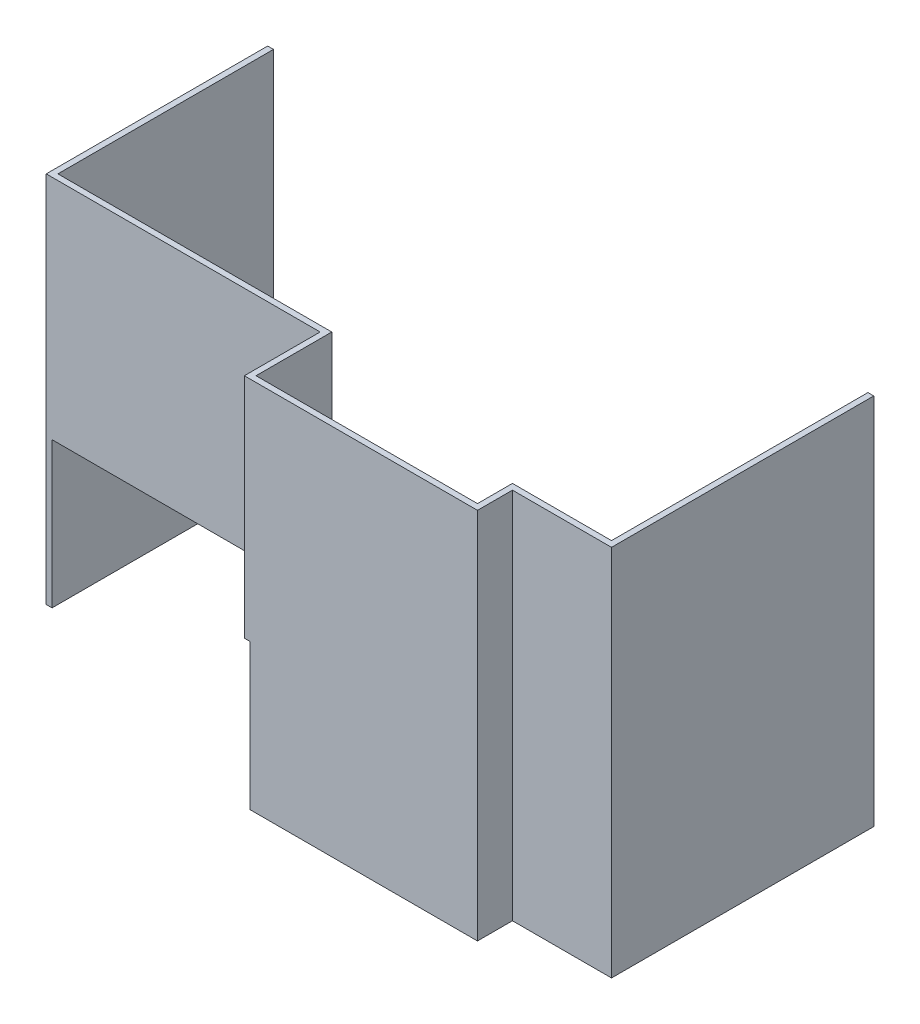
SolidWorks part; units mm, degrees
ref_plane "Front Plane" through (0, 0, 0) normal (0, 0, 1) x (1, 0, 0)
ref_plane "Top Plane" through (0, 0, 0) normal (0, 1, 0) x (1, 0, 0)
ref_plane "Right Plane" through (0, 0, 0) normal (1, 0, 0) x (0, 0, -1)
sketch "Sketch1" plane through (0, 0, 0) normal (0, 1, 0) x (1, 0, 0)
  line L0 (0, 0) -> (0, 241.3)
  line L1 (0, 241.3) -> (6.35, 241.3)
  line L2 (6.35, 241.3) -> (6.35, 6.35)
  line L3 (6.35, 6.35) -> (304.8, 6.35)
  line L4 (0, 0) -> (298.45, 0)
  line L5 (298.45, 0) -> (298.45, -82.55)
  line L6 (298.45, -82.55) -> (552.45, -82.55)
  line L8 (552.45, -44.45) -> (660.4, -44.45)
  line L9 (660.4, -44.45) -> (660.4, 241.3)
  line L10 (660.4, 241.3) -> (654.05, 241.3)
  line L11 (654.05, 241.3) -> (654.05, -38.1)
  line L12 (654.05, -38.1) -> (546.1, -38.1)
  line L14 (546.1, -76.2) -> (304.8, -76.2)
  line L15 (304.8, -76.2) -> (304.8, 6.35)
  line L16 (546.1, -38.1) -> (546.1, -76.2)
  line L17 (552.45, -82.55) -> (552.45, -44.45)
  dimension "D1" = 241.3
  dimension "D2" = 6.35
  dimension "D3" = 6.35
  dimension "D4" = 6.35
  dimension "D5" = 6.35
  dimension "D6" = 6.35
  dimension "D7" = 6.35
  dimension "D8" = 6.35
  dimension "D9" = 660.4
  dimension "D10" = 254
  dimension "D11" = 107.95
  dimension "D12" = 90
  dimension "D13" = 82.55
  dimension "D14" = 6.35
  dimension "D15" = 38.1
extrude "Boss-Extrude1" add sketch "Sketch1" along normal blind 406.4
sketch "Sketch2" plane through (0, 0, 82.55) normal (0, 0, 1) x (1, 0, 0)
  line L0 (298.45, 0) -> (552.45, 0) construction
  line L1 (304.8, 0) -> (88.9, 0)
  line L2 (304.8, 0) -> (304.8, 158.75)
  line L3 (304.8, 158.75) -> (6.35, 158.75)
  line L5 (6.35, 406.4) -> (6.35, 0) construction
  line L6 (88.9, 0) -> (6.35, 0)
  line L11 (6.35, 0) -> (6.35, 158.75)
  line L13 (304.8, 406.4) -> (304.8, 0) construction
  dimension "D1" = 158.75
extrude "Cut-Extrude1" cut sketch "Sketch2" against normal up to surface (88.9 mm away) up to face at (155.575, 203.2, -6.35)
